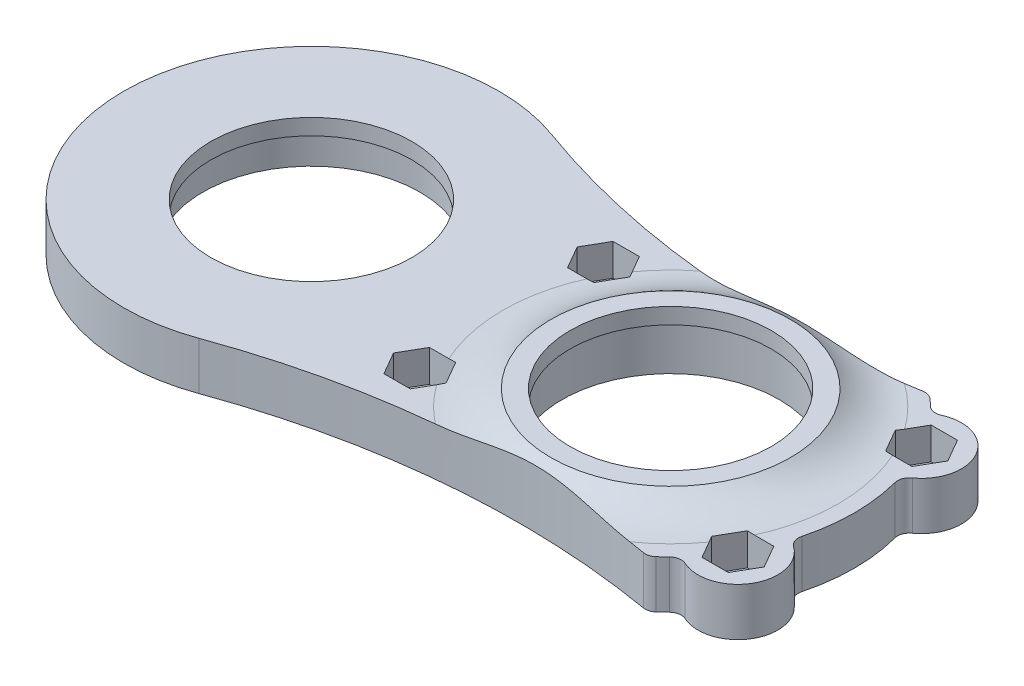
SolidWorks part; units mm, degrees
material "ABS"
ref_plane "前视基准面" through (0, 0, 0) normal (0, 0, 1) x (1, 0, 0)
ref_plane "上视基准面" through (0, 0, 0) normal (0, 1, 0) x (1, 0, 0)
ref_plane "右视基准面" through (0, 0, 0) normal (1, 0, 0) x (0, 0, -1)
sketch "草图1" plane through (0, 0, 0) normal (0, 1, 0) x (1, 0, 0)
  line L1 (-19.9186, -11.5) -> (19.9186, -11.5)
  line L2 (-19.9186, -11.5) -> (-19.9186, 11.5)
  line L3 (-19.9186, 11.5) -> (19.9186, 11.5)
  line L4 (19.9186, -11.5) -> (19.9186, 11.5)
  line L5 (-19.9186, -11.5) -> (19.9186, 11.5) construction
  line L6 (-19.9186, 11.5) -> (19.9186, -11.5) construction
  circle A0 centre (0, 0) radius 23
  circle A1 centre (-19.9186, -11.5) radius 5
  circle A2 centre (19.9186, -11.5) radius 5
  circle A3 centre (19.9186, 11.5) radius 5
  circle A4 centre (-19.9186, 11.5) radius 5
  circle A5 centre (0, 0) radius 13.6
  dimension "D1" = 46
  dimension "D3" = 10
  dimension "D4" = 10
  dimension "D5" = 10
  dimension "D6" = 10
  dimension "D7" = 27.2
  dimension "D2" = 60
extrude "凸台-拉伸1" add sketch "草图1" against normal blind 6 contours A4 A0 A1 L2 | A0 A4 L2 | L2 A4 L3 | L3 A4 A0 | A0 A4 | A5 L3 A3 A0 A4 | A5 L3 A4 L2 A1 L1 | A0 A1 | A0 A1 L1 | L2 A1 A0 | L1 A1 L2 | A0 A3 L3 | A0 A3 | L3 A3 L4 | L4 A3 A0 | A3 L4 A2 A0 | L4 A2 L1 | A0 A2 L4 | A0 A2 | L1 A2 A0 | A5 L1 A1 A0 A2 | A5 L1 A2 L4 A3 L3 region at (-17.7965, 0, 9.3779) region at (-20.6302, 0, 8.3398) region at (-21.669, 0, 12.5106) region at (-17.1067, 0, 12.9746) region at (-15.0595, 0, 0) region at (0, 0, 16.7833) region at (-21.3211, 0, 0) region at (-20.6302, 0, -8.3398) region at (-17.7965, 0, -9.3779) region at (-21.669, 0, -12.5106) region at (17.1067, 0, 12.9746) region at (21.669, 0, 12.5106) region at (15.0595, 0, 0) region at (0, 0, -16.7833) region at (-17.1067, 0, -12.9746) region at (17.7965, 0, 9.3779) region at (20.6302, 0, 8.3398) region at (21.669, 0, -12.5106) region at (17.1067, 0, -12.9746) region at (21.3211, 0, 0) region at (17.7965, 0, -9.3779) region at (20.6302, 0, -8.3398)
sketch "草图2" plane through (0, -6, 0) normal (0, -1, 0) x (1, 0, 0)
  line L1 (19.9186, -11.5) -> (-19.9186, -11.5)
  line L2 (19.9186, -11.5) -> (19.9186, 11.5)
  line L3 (19.9186, 11.5) -> (-19.9186, 11.5)
  line L4 (-19.9186, -11.5) -> (-19.9186, 11.5)
  line L5 (19.9186, -11.5) -> (-19.9186, 11.5) construction
  line L6 (19.9186, 11.5) -> (-19.9186, -11.5) construction
  circle A0 centre (-19.9186, 11.5) radius 1.6
  circle A1 centre (-19.9186, -11.5) radius 1.6
  point P0 (0, 0)
  dimension "D1" = 3.2
  dimension "D2" = 3.2
extrude "切除-拉伸1" cut sketch "草图2" against normal blind 14 contours L3 A0 L4 | L4 A0 L3 | L4 A1 L1 | L1 A1 L4 region at (-20.1449, -6, -11.7264) region at (-19.2395, -6, -10.8209) region at (-19.2395, -6, 10.8209) region at (-20.1449, -6, 11.7264)
pattern_circular "阵列(圆周)1" count 2 over 360 about axis through (0, -6, 0) along (0, 1, 0) of "切除-拉伸1"
sketch "草图3" plane through (0, -6, 0) normal (0, -1, 0) x (1, 0, 0)
  arc A0 (42.2289, -26.7852) -> (-36.9716, -22.0861) centre (-2.8082, -116.0694) ccw construction
  arc A1 (42.2289, -26.7852) -> (-36.9716, -22.0861) centre (-2.8082, -116.0694) ccw
  arc A2 (-36.9716, 22.0861) -> (42.2289, 26.7852) centre (-2.8082, 116.0694) ccw construction
  arc A3 (-36.9716, 22.0861) -> (42.2289, 26.7852) centre (-2.8082, 116.0694) ccw
  circle A4 centre (0, 0) radius 23
  arc A8 (21.9331, 6.9238) -> (16.9627, 15.5327) centre (19.9186, 11.5) ccw
  arc A9 (16.9627, 15.5327) -> (-16.9627, 15.5327) centre (0, 0) ccw
  arc A10 (-16.9627, 15.5327) -> (-21.9331, 6.9238) centre (-19.9186, 11.5) ccw
  arc A11 (-21.9331, 6.9238) -> (-21.9331, -6.9238) centre (0, 0) ccw
  arc A12 (-21.9331, -6.9238) -> (-16.9627, -15.5327) centre (-19.9186, -11.5) ccw
  arc A13 (-16.9627, -15.5327) -> (16.9627, -15.5327) centre (0, 0) ccw
  arc A14 (16.9627, -15.5327) -> (21.9331, -6.9238) centre (19.9186, -11.5) ccw
  arc A15 (21.9331, -6.9238) -> (21.9331, 6.9238) centre (0, 0) ccw
  arc A16 (21.9331, 6.9238) -> (16.9627, 15.5327) centre (19.9186, 11.5) ccw
  arc A17 (16.9627, 15.5327) -> (-16.9627, 15.5327) centre (0, 0) ccw
  arc A18 (-16.9627, 15.5327) -> (-21.9331, 6.9238) centre (-19.9186, 11.5) ccw
  arc A19 (-21.9331, 6.9238) -> (-21.9331, -6.9238) centre (0, 0) ccw
  arc A20 (-21.9331, -6.9238) -> (-16.9627, -15.5327) centre (-19.9186, -11.5) ccw
  arc A21 (-16.9627, -15.5327) -> (16.9627, -15.5327) centre (0, 0) ccw
  arc A22 (16.9627, -15.5327) -> (21.9331, -6.9238) centre (19.9186, -11.5) ccw
  arc A23 (21.9331, -6.9238) -> (21.9331, 6.9238) centre (0, 0) ccw
  arc M15 (16.9627, 15.5327) -> (-16.9627, 15.5327) centre (0, 0) ccw
  arc M19 (-16.9627, -15.5327) -> (16.9627, -15.5327) centre (0, 0) ccw
  dimension "D1" = 0
extrude "切除-拉伸2" cut sketch "草图3" against normal blind 7 contours A3 M15 | A1 M19 region at (-0.4626, -6, -19.1208) region at (-0.4626, -6, 19.1208)
fillet "圆角1" radius 1.5 12 edges at (-16.9627, -3, 15.5327) (-21.9331, -3, 6.9238) (-21.9331, -3, -6.9238) (-16.9627, -3, -15.5327) (-15.6095, -3, -16.8921) (14.7743, -3, -17.6273) (16.9627, -3, -15.5327) (21.9331, -3, -6.9238) (21.9331, -3, 6.9238) (16.9627, -3, 15.5327) (14.7743, -3, 17.6273) (-15.6095, -3, 16.8921)
sketch "草图4" plane through (0, -6, 0) normal (0, -1, 0) x (1, 0, 0)
  line L1 (-15.8771, 11.5) -> (-17.8979, 15)
  line L2 (-17.8979, 15) -> (-21.9393, 15)
  line L3 (-21.9393, 15) -> (-23.96, 11.5)
  line L4 (-23.96, 11.5) -> (-21.9393, 8)
  line L5 (-21.9393, 8) -> (-17.8979, 8)
  line L6 (-17.8979, 8) -> (-15.8771, 11.5)
  circle A0 centre (-19.9186, 11.5) radius 3.5 construction
  circle A1 centre (-19.9186, 11.5) radius 5.5
  dimension "D2" = 11
  dimension "D1" = 7
sketch "草图5" plane through (0, -6, 0) normal (0, -1, 0) x (1, 0, 0)
  line L1 (-23.96, 11.5) -> (-21.9393, 8)
  line L2 (-21.9393, 8) -> (-17.8979, 8)
  line L3 (-17.8979, 8) -> (-15.8771, 11.5)
  line L4 (-15.8771, 11.5) -> (-17.8979, 15)
  line L5 (-17.8979, 15) -> (-21.9393, 15)
  line L6 (-21.9393, 15) -> (-23.96, 11.5)
  circle A0 centre (-19.9186, 11.5) radius 3.5 construction
sketch "草图7" plane through (0, -6, 0) normal (0, -1, 0) x (1, 0, 0)
  circle A0 centre (0, 0) radius 13.6
  circle A1 centre (0, 0) radius 12.6
  circle A2 centre (0, 0) radius 13.6 construction
  dimension "D1" = 1
  dimension "D2" = 0
sketch "草图8" plane through (0, 0, 0) normal (0, 1, 0) x (1, 0, 0)
  line L1 (-16.6277, 11.5) -> (-18.2731, 14.35)
  line L2 (-18.2731, 14.35) -> (-21.564, 14.35)
  line L3 (-21.564, 14.35) -> (-23.2095, 11.5)
  line L4 (-23.2095, 11.5) -> (-21.564, 8.65)
  line L5 (-21.564, 8.65) -> (-18.2731, 8.65)
  line L6 (-18.2731, 8.65) -> (-16.6277, 11.5)
  line L7 (-16.6277, -11.5) -> (-18.2731, -8.65)
  line L8 (-18.2731, -8.65) -> (-21.564, -8.65)
  line L9 (-21.564, -8.65) -> (-23.2095, -11.5)
  line L10 (-23.2095, -11.5) -> (-21.564, -14.35)
  line L11 (-21.564, -14.35) -> (-18.2731, -14.35)
  line L12 (-18.2731, -14.35) -> (-16.6277, -11.5)
  circle A0 centre (-19.9186, 11.5) radius 2.85 construction
  circle A1 centre (-19.9186, -11.5) radius 2.85 construction
  dimension "D1" = 5.7
  dimension "D2" = 5.7
extrude "切除-拉伸4" cut sketch "草图8" against normal blind 4
pattern_circular "阵列(圆周)2" count 6 over 360 about axis through (0, -6, 0) along (0, 1, 0) of "切除-拉伸4" reverse direction yes
sketch "草图9" plane through (0, 0, 0) normal (0, 1, 0) x (1, 0, 0)
  circle A0 centre (0, 0) radius 12.6
  circle A1 centre (0, 0) radius 13.6
extrude "凸台-拉伸5" add sketch "草图9" against normal blind 2
sketch "草图12" plane through (0, -6, 0) normal (0, -1, 0) x (1, 0, 0)
  line L0 (0, 0) -> (-45, 0)
  line L2 (-8.5504, -23.5018) -> (-81.4496, -23.5018)
  line L3 (-8.5504, -23.5018) -> (-8.5504, 23.5018)
  line L4 (-8.5504, 23.5018) -> (-81.4496, 23.5018)
  line L5 (-81.4496, -23.5018) -> (-81.4496, 23.5018)
  line L6 (-8.5504, -23.5018) -> (-81.4496, 23.5018) construction
  line L7 (-8.5504, 23.5018) -> (-81.4496, -23.5018) construction
  circle A0 centre (-45, 0) radius 13.6
  arc M11 (14.078, 17.5054) -> (-14.9081, 16.8041) centre (-2.8082, 116.0694) cw
  arc M12 (-14.9081, 16.8041) -> (-16.1424, 16.3836) centre (-15.0896, 15.3152) ccw
  arc M13 (-16.1424, 16.3836) -> (-16.175, 16.3514) centre (0, 0) ccw
  arc M14 (-16.175, 16.3514) -> (-17.8503, 16.0522) centre (-17.2299, 17.4178) cw
  arc M15 (-17.8503, 16.0522) -> (-22.8268, 7.4328) centre (-19.9186, 11.5) ccw
  arc M16 (-22.8268, 7.4328) -> (-22.2483, 5.8322) centre (-23.6992, 6.2126) cw
  arc M17 (-22.2483, 5.8322) -> (-22.2483, -5.8322) centre (0, 0) ccw
  arc M18 (-22.2483, -5.8322) -> (-22.8268, -7.4328) centre (-23.6992, -6.2126) cw
  arc M19 (-22.8268, -7.4328) -> (-17.8503, -16.0522) centre (-19.9186, -11.5) ccw
  arc M20 (-17.8503, -16.0522) -> (-16.175, -16.3514) centre (-17.2299, -17.4178) cw
  arc M21 (-16.175, -16.3514) -> (-16.1424, -16.3836) centre (0, 0) ccw
  arc M22 (-16.1424, -16.3836) -> (-14.9081, -16.8041) centre (-15.0896, -15.3152) ccw
  arc M23 (-14.9081, -16.8041) -> (14.078, -17.5054) centre (-2.8082, -116.0694) cw
  dimension "D1" = 27.2
  dimension "D2" = 45
extrude "凸台-拉伸6" add sketch "草图12" against normal up to surface (6 mm away) contours A0 L3 L4 L5 L2 M17 M16 M15 M14 M13 M12 M11 M23 M22 M21 M20 M19 M18 region at (-23.6716, -6, -3.0511) up to face at (19.9186, 0, -11.5)
sketch "草图15" plane through (0, 0, 0) normal (0, 1, 0) x (1, 0, 0)
  line L1 (-8.5504, -23.5018) -> (-81.4496, -23.5018)
  line L2 (-8.5504, -23.5018) -> (-8.5504, 23.5018)
  line L3 (-8.5504, 23.5018) -> (-81.4496, 23.5018)
  line L4 (-81.4496, -23.5018) -> (-81.4496, 23.5018)
  line L5 (-8.5504, -23.5018) -> (-81.4496, 23.5018) construction
  line L6 (-8.5504, 23.5018) -> (-81.4496, -23.5018) construction
  circle A0 centre (-2.8082, 116.0694) radius 100
  circle A1 centre (-2.8082, -116.0694) radius 100
  circle A2 centre (-45, 0) radius 23.5
  line M2 (-8.5504, 16.2344) -> (-8.5504, 23.5018)
  line M3 (-8.5504, 23.5018) -> (-81.4496, 23.5018)
  line M4 (-81.4496, 23.5018) -> (-81.4496, -23.5018)
  line M5 (-81.4496, -23.5018) -> (-8.5504, -23.5018)
  line M6 (-8.5504, -23.5018) -> (-8.5504, -16.2344)
extrude "切除-拉伸5" cut sketch "草图15" against normal blind 10 contours A2 A0 L3 A1 M4 M5 | A0 M3 M2 | A1 L1 M6 region at (-20.3638, 0, 20.7233) region at (-71.6071, 0, 0) region at (-20.3638, 0, -20.7233)
sketch "草图16" plane through (0, -6, 0) normal (0, -1, 0) x (1, 0, 0)
  circle A0 centre (-45, 0) radius 12.6
  dimension "D1" = 25.2
sketch "草图17" plane through (0, 0, 0) normal (0, 1, 0) x (1, 0, 0)
  circle A0 centre (-45, 0) radius 12.6
  circle A1 centre (-45, 0) radius 13.6
  dimension "D1" = 25.2
extrude "凸台-拉伸7" add sketch "草图17" against normal up to surface (2 mm away) up to face at (0, -2, 12.6)
sketch "草图18" plane through (0, 0, 0) normal (0, 1, 0) x (1, 0, 0)
  circle A0 centre (0, 0) radius 15
  circle A2 centre (0, 0) radius 13.6
  dimension "D1" = 30
  dimension "D2" = 27.2
extrude "凸台-拉伸8" add sketch "草图18" along normal blind 2
sketch "草图19" plane through (0, 0, 0) normal (0, 1, 0) x (1, 0, 0)
  circle A0 centre (0, 0) radius 13.6
extrude "切除-拉伸6" cut sketch "草图19" against normal blind 2
sketch "草图20" plane through (0, 2, 0) normal (0, 1, 0) x (1, 0, 0)
  circle A0 centre (0, 0) radius 13.6
  circle A1 centre (0, 0) radius 12.6
  circle A2 centre (0, 0) radius 13.6 construction
  dimension "D1" = 1
  dimension "D2" = 0
extrude "凸台-拉伸9" add sketch "草图20" against normal blind 2 separate body
combine bodies "组合1" operation type add bodies to combine 122 121
fillet "圆角2" radius 10 1 edges at (0, 0, 15)
